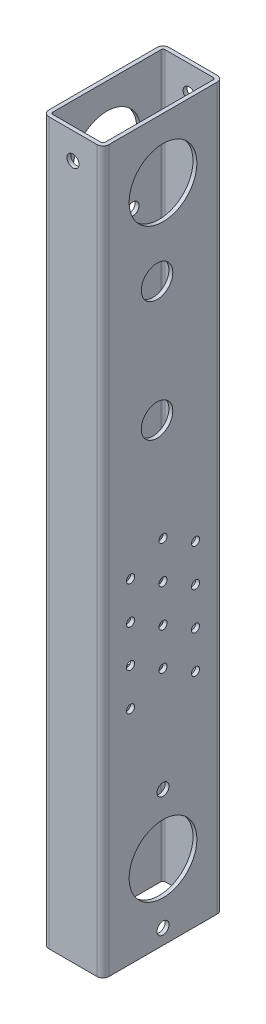
SolidWorks part; units mm, degrees
material "6061-T6 (SS)"
ref_plane "Front Plane" through (0, 0, 0) normal (0, 0, 1) x (1, 0, 0)
ref_plane "Top Plane" through (0, 0, 0) normal (0, 1, 0) x (1, 0, 0)
ref_plane "Right Plane" through (0, 0, 0) normal (1, 0, 0) x (0, 0, -1)
sketch "Sketch1" plane through (0, 0, 0) normal (0, 1, 0) x (1, 0, 0)
  line L1 (10.16, -25.4) -> (-10.16, -25.4)
  line L2 (12.7, -22.86) -> (12.7, 22.86)
  line L3 (10.16, 25.4) -> (-10.16, 25.4)
  line L4 (-12.7, -22.86) -> (-12.7, 22.86)
  line L5 (12.7, -25.4) -> (-12.7, 25.4) construction
  line L6 (12.7, 25.4) -> (-12.7, -25.4) construction
  arc A0 (-10.16, -25.4) -> (-12.7, -22.86) centre (-10.16, -22.86) cw
  arc A1 (10.16, -25.4) -> (12.7, -22.86) centre (10.16, -22.86) ccw
  arc A2 (12.7, 22.86) -> (10.16, 25.4) centre (10.16, 22.86) ccw
  arc A3 (-10.16, 25.4) -> (-12.7, 22.86) centre (-10.16, 22.86) ccw
  point P0 (0, 0)
  dimension "D3" = 2.54
  dimension "D1" = 25.4
  dimension "D2" = 50.8
extrude "Extrude-Thin1" add sketch "Sketch1" along normal blind 222.25 and the other way blind 82.55 thin thin type one direction reverse wall 1.651
sketch "Sketch2" plane through (-12.7, 0, 0) normal (-1, 0, 0) x (0, 0, 1)
  line L0 (2.54, 161.9426) -> (2.54, 12.7) construction
  line L4 (9.2075, 161.9426) -> (9.2075, 12.7)
  line L5 (-4.1275, 161.9426) -> (-4.1275, 12.7)
  line L6 (2.54, 25.4) -> (2.54, 149.2426) construction
  arc A2 (9.2075, 161.9426) -> (-4.1275, 161.9426) centre (2.54, 161.9426) ccw
  arc A3 (-4.1275, 12.7) -> (9.2075, 12.7) centre (2.54, 12.7) ccw
  point P3 (2.54, 87.3213)
  dimension "D5" = 13.335
  dimension "D2" = 12.7
  dimension "D1" = 12.7
extrude "Cut-Extrude1" cut sketch "Sketch2" against normal up to next
sketch "Sketch5" plane through (12.7, 0, 0) normal (1, 0, 0) x (0, 0, -1)
  circle A3 centre (-2.54, 111.1426) radius 6.6675 construction
  circle A4 centre (-2.54, 111.1426) radius 6.6675
  circle A5 centre (-2.54, 161.9426) radius 6.6675 construction
  circle A6 centre (-2.54, 161.9426) radius 6.6675
extrude "Cut-Extrude4" cut sketch "Sketch5" against normal up to next
sketch "Sketch4" plane through (-12.7, 0, 0) normal (1, 0, 0) x (0, 0, -1)
  circle A12 centre (11.049, 4.7713) radius 2.5527
  circle A13 centre (-16.129, 4.7713) radius 2.5527
  circle A14 centre (-16.129, 87.3213) radius 2.5527
  circle A15 centre (11.049, 87.3213) radius 2.5527
  circle A16 centre (-16.129, 169.8713) radius 2.5527
  circle A17 centre (11.049, 169.8713) radius 2.5527
  dimension "D1" = 5.1054
extrude "Cut-Extrude3" cut sketch "Sketch4" along normal up to surface (1.651 mm away) up to face at (-11.049, 87.3213, 2.54)
sketch "Sketch6" plane through (12.7, 0, 0) normal (1, 0, 0) x (0, 0, -1)
  line L0 (25.4, -82.55) -> (25.4, 222.25) construction
  circle A0 centre (0, -50.8) radius 14.3256
  circle A1 centre (0, 196.85) radius 14.3256
  dimension "D1" = 28.6512
  dimension "D2" = 25.4
  dimension "D3" = 50.8
  dimension "D4" = 247.65
extrude "Cut-Extrude5" cut sketch "Sketch6" against normal through all
hole_wizard "#10 Clearance Hole1" positions "Sketch8" profile "Sketch9" hole size "#10" standard "ANSI Inch" end condition through all
sketch "Sketch8" plane through (12.7, 0, 0) normal (1, 0, 0) x (0, 0, -1)
  circle A0 centre (0, -50.8) radius 25.4 construction
  point P0 (0, -25.4)
  point P11 (0, -76.2)
  dimension "D1" = 50.8
sketch "Sketch9" plane through (12.7, -25.4, 0) normal (0, 1, 0) x (0, 0, -1)
  line L0 (0, 0) -> (0, 25.4)
  line L1 (0, 25.4) -> (2.5527, 25.4)
  line L2 (2.5527, 25.4) -> (2.5527, 0)
  line L5 (2.5527, 0) -> (0, 0)
  line L11 (0, -6.35) -> (0, 107.95) construction
  dimension "Thru Hole Dia." = 5.1054
  dimension "Thru Hole Depth" = 25.4
hole_wizard "1/8 (0.135) Diameter Hole1" positions "Sketch10" profile "Sketch11" hole size "1/8" standard "ANSI Inch" end condition up to next
sketch "Sketch10" plane through (12.7, 0, 0) normal (1, 0, 0) x (0, 0, -1)
  point P39 (0, 66.5303)
  point P42 (13.7482, 58.5928)
  point P45 (-13.7482, 58.5928)
  point P48 (0, 50.6553)
  point P51 (0, 34.7803)
  point P54 (-13.7482, 42.7178)
  point P57 (13.7482, 26.8428)
  point P60 (13.7482, 42.7178)
  point P63 (0, 18.9053)
  point P66 (-13.7482, 26.8428)
  point P69 (-13.7482, 10.9678)
  point P72 (13.7482, 10.9678)
sketch "Sketch11" plane through (12.7, 66.5303, 0) normal (0, 1, 0) x (0, 0, -1)
  line L0 (0, 0) -> (0, 1.651)
  line L1 (0, 1.651) -> (1.7145, 1.651)
  line L2 (1.7145, 1.651) -> (1.7145, 0)
  line L5 (1.7145, 0) -> (0, 0)
  line L11 (0, -6.35) -> (0, 107.95) construction
  dimension "Thru Hole Dia." = 3.429
  dimension "Thru Hole Depth" = 1.651
hole_wizard "1/8 (0.135) Diameter Hole2" positions "Sketch12" profile "Sketch13" hole size "1/8" standard "ANSI Inch" end condition up to next
sketch "Sketch12" plane through (-12.7, 0, 0) normal (-1, 0, 0) x (0, 0, 1)
  point P0 (17.399, 63.3553)
  point P3 (17.399, 53.8303)
  point P6 (17.399, 44.3053)
  point P9 (17.399, 34.7803)
  point P12 (17.399, 25.2553)
  point P15 (17.399, 15.7303)
sketch "Sketch13" plane through (-12.7, 63.3553, 17.399) normal (0, 1, 0) x (0, 0, 1)
  line L0 (0, 0) -> (0, 1.651)
  line L1 (0, 1.651) -> (1.7145, 1.651)
  line L2 (1.7145, 1.651) -> (1.7145, 0)
  line L5 (1.7145, 0) -> (0, 0)
  line L11 (0, -6.35) -> (0, 107.95) construction
  dimension "Thru Hole Dia." = 3.429
  dimension "Thru Hole Depth" = 1.651
hole_wizard "#10 Clearance Hole2" positions "Sketch14" profile "Sketch15" hole size "#10" standard "ANSI Inch" end condition through all
sketch "Sketch14" plane through (0, 0, -25.4) normal (0, 0, -1) x (-1, 0, 0)
  point P0 (0, 211.1375)
sketch "Sketch15" plane through (0, 211.1375, -25.4) normal (1, 0, 0) x (0, 1, 0)
  line L0 (0, 0) -> (0, 50.8)
  line L1 (0, 50.8) -> (2.5527, 50.8)
  line L2 (2.5527, 50.8) -> (2.5527, 0)
  line L5 (2.5527, 0) -> (0, 0)
  line L11 (0, -6.35) -> (0, 107.95) construction
  dimension "Thru Hole Dia." = 5.1054
  dimension "Thru Hole Depth" = 50.8
move or copy body "Body-Move/Copy1" [suppressed] bodies to move or copy 110 parameters "D1"=0, "D2"=0, "D3"=0
